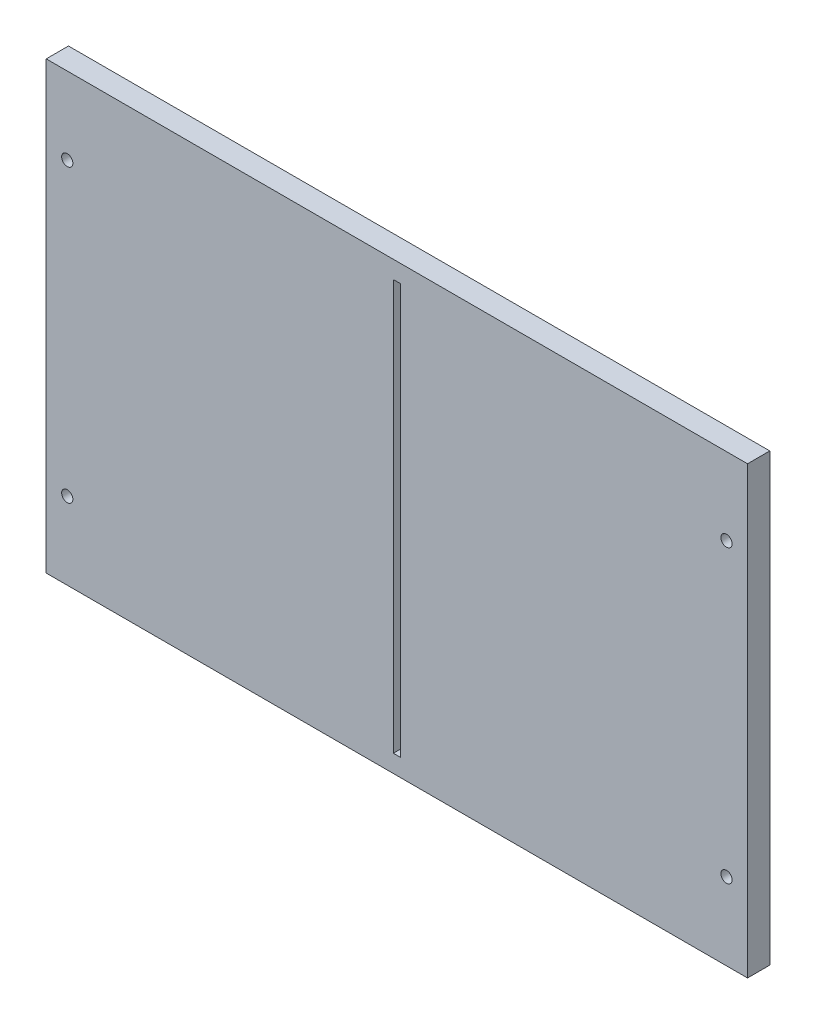
SolidWorks part; units mm, degrees
ref_plane "Front Plane" through (0, 0, 0) normal (0, 0, 1) x (1, 0, 0)
ref_plane "Top Plane" through (0, 0, 0) normal (0, 1, 0) x (1, 0, 0)
ref_plane "Right Plane" through (0, 0, 0) normal (1, 0, 0) x (0, 0, -1)
sketch "Sketch1" plane through (0, 0, 0) normal (0, 0, 1) x (1, 0, 0)
  line L0 (100, 127) -> (100, 0) construction
  line L1 (0, 0) -> (200, 0)
  line L2 (0, 0) -> (0, 127)
  line L3 (0, 127) -> (200, 127)
  line L4 (200, 0) -> (200, 127)
  line L5 (0, 63.5) -> (200, 63.5) construction
  circle A3 centre (6, 105) radius 1.6
  circle A7 centre (194, 105) radius 1.6
  circle A8 centre (194, 22) radius 1.6
  circle A9 centre (6, 22) radius 1.6
  dimension "D11" = 3.2
  dimension "D1" = 127
  dimension "D2" = 200
  dimension "D12" = 6
  dimension "D13" = 22
extrude "Wall" add sketch "Sketch1" along normal blind 6.35
sketch "Sketch2" [suppressed] plane through (0, 0, 6.35) normal (0, 0, 1) x (1, 0, 0)
  line L0 (135.35, 127) -> (135.35, 98.425) construction
  line L1 (270.7, 127) -> (0, 127) construction
  line L2 (135.35, 98.425) -> (66.6667, 98.425) construction
  line L3 (135.35, 98.425) -> (204.0333, 98.425) construction
  line L4 (0, 127) -> (0, 0) construction
  circle A0 centre (135.35, 98.425) radius 3.9687
  circle A1 centre (66.6667, 98.425) radius 3.9688
  circle A2 centre (204.0333, 98.425) radius 3.9687
  dimension "D2" = 7.9375
  dimension "D1" = 28.575
  dimension "D3" = 66.6667
extrude "RodSupportCutouts" [suppressed] cut sketch "Sketch2" against normal up to next
sketch "Sketch3" [suppressed] plane through (0, 0, 6.35) normal (0, 0, 1) x (1, 0, 0)
  line L1 (25.4, 88.9) -> (245.3, 88.9)
  line L2 (25.4, 88.9) -> (25.4, 114.3)
  line L3 (25.4, 114.3) -> (245.3, 114.3)
  line L4 (245.3, 88.9) -> (245.3, 114.3)
  line L5 (25.4, 88.9) -> (245.3, 114.3) construction
  line L6 (25.4, 114.3) -> (245.3, 88.9) construction
  line L7 (270.7, 127) -> (0, 127) construction
  line L8 (0, 127) -> (0, 0) construction
  point P0 (135.35, 101.6)
  point P9 (135.35, 127)
  dimension "D1" = 25.4
  dimension "D2" = 25.4
  dimension "D3" = 25.4
extrude "CannulaLargeCutout" [suppressed] cut sketch "Sketch3" against normal up to next
sketch "Sketch4" [suppressed] plane through (0, 0, 9.525) normal (0, 0, 1) x (1, 0, 0)
  line L0 (6, 103.5) -> (194, 103.5) construction
  line L1 (6, 105) -> (6, 22) construction
  line L2 (194, 105) -> (194, 22) construction
  line L3 (200, 127) -> (0, 127) construction
  line L4 (0, 127) -> (0, 0) construction
  circle A0 centre (60, 103.5) radius 6.35
  circle A1 centre (20, 103.5) radius 6.35
  circle A2 centre (100, 103.5) radius 6.35
  circle A3 centre (140, 103.5) radius 6.35
  circle A4 centre (60, 63.5) radius 6.35
  circle A5 centre (100, 63.5) radius 6.35
  circle A6 centre (140, 63.5) radius 6.35
  circle A7 centre (60, 23.5) radius 6.35
  circle A8 centre (100, 23.5) radius 6.35
  circle A9 centre (140, 23.5) radius 6.35
  circle A10 centre (20, 63.5) radius 6.35
  circle A11 centre (20, 23.5) radius 6.35
  circle A12 centre (180, 103.5) radius 6.35
  circle A13 centre (180, 63.5) radius 6.35
  circle A14 centre (180, 23.5) radius 6.35
  point P42 (100, 127)
  point P45 (0, 63.5)
  dimension "D3" = 12.7
  dimension "D1" = 5
  dimension "D2" = 3
extrude "CannulaHoles" [suppressed] cut sketch "Sketch4" against normal up to next
ref_plane "LeftBoundary" [suppressed] through (25.4, 0, 0) normal (-1, 0, 0) x (0, 0, 1)
ref_plane "RightBoundary" [suppressed] through (245.3, 0, 0) normal (1, 0, 0) x (0, 0, -1)
ref_plane "TopBoundary" [suppressed] through (0, 101.6, 0) normal (0, 1, 0) x (1, 0, 0)
ref_plane "BottomBoundary" [suppressed] through (0, 25.4, 0) normal (0, -1, 0) x (-1, 0, 0)
sketch "Sketch5" [suppressed] plane through (0, 0, 6.35) normal (0, 0, 1) x (1, 0, 0)
  line L4 (25.4, 3.4925) -> (25.4, -3.4925) construction
  line L5 (3.4925, 101.6) -> (-3.4925, 101.6) construction
  circle A0 centre (25.4, 101.6) radius 3.9687
  dimension "D1" = 7.9375
extrude "RodSupportCutout" [suppressed] cut sketch "Sketch5" along normal blind 3.35 from surface starting at face at (4.4, 22, 0)
pattern_linear "SupportPattern" [suppressed] count 7 spacing 36.65 count 5 spacing 19.05 of bodies 105
sketch "Sketch6" plane through (0, 0, 6.35) normal (0, 0, 1) x (1, 0, 0)
  line L1 (99, 122) -> (101, 122)
  line L2 (99, 122) -> (99, 5)
  line L3 (99, 5) -> (101, 5)
  line L4 (101, 122) -> (101, 5)
  line L9 (0, 0) -> (200, 0) construction
  line L10 (200, 0) -> (200, 127) construction
  point P7 (200, 57)
  dimension "D1" = 117
  dimension "D2" = 5
  dimension "D3" = 2
  dimension "D4" = 99
extrude "Cut-Extrude1" cut sketch "Sketch6" against normal through all
equation "\"Length\"= 283mm"
equation "\"Width\"= 225mm"
equation "\"WallThickness\"= 0.25in"
equation "\"UpperWaterJacketThickness\"= 28mm"
equation "\"SpacerHeight\"= 80.2mm"
equation "\"SpacerCornerWidth\"= 10mm"
equation "\"SpacerCornerHeight\"= 60.16mm"
equation "\"SpacerPegDiameter\"= 10mm"
equation "\"SpacerPegHeight\"= 10mm"
equation "\"TubingShort\"= 110mm"
equation "\"TubingLong\"= 175mm"
equation "\"PlateLength\"= 252mm"
equation "\"PlateWidth\"= 190mm"
equation "\"PlateHoleDiameter\"= 5.9mm"
equation "\"PlateHoleBottom\"= 2mm"
equation "\"PlateHoleSide\"= 1.55mm"
equation "\"PlateHoleSpacing\"= 3.1mm"
equation "\"PlateThickness\"= 1.55mm"
equation "\"ReservoirBottom\"= 12.5mm"
equation "\"ReservoirSupportWidth\"= 12mm"
equation "\"ReservoirSupportHeight\"= 15.1mm"
equation "\"ReservoirSupportPlacementHeight\"= 50mm"
equation "\"ReservoirHoleDiameter\"= 12.7mm"
equation "\"ReservoirHoleRight\"= 25mm"
equation "\"ReservoirHoleTop\"= \"ReservoirSupportPlacementHeight\""
equation "\"ReservoirHeight\"= 90mm"
equation "\"ReservoirPortBottom\"= 4mm"
equation "\"ReservoirPortTop\"= 10mm"
equation "\"ReservoirPortWidth\"= 101mm"
equation "\"CustomSpacerHeight\"= 5in"
equation "\"CustomSpacerRodHoleHeight\"= .75in"
equation "\"CustomSpacerRodHoleDiameter\"= .3125in"
equation "\"ScrewBlockSide\"= 12mm"
equation "\"ScrewBlockUpperHeight\"= 16mm"
equation "\"ScrewBlockLowerHeight\"= 16mm"
equation "\"InternalLength\"= 258mm"
equation "\"InternalWidth\"= 200mm"
equation "\"CustomSpacerPegHeight\"= 1in"
equation "\"CustomSpacerScrewBore\"=3.2mm"
equation "\"CustomSpacerScrewDepth\"=10mm"
equation "\"D1@Sketch1\"=\"CustomSpacerHeight\""
equation "\"D2@Sketch1\"=\"WallLength\""
equation "\"D11@Sketch1\"=\"CustomSpacerScrewBore\""
equation "\"D12@Sketch1\"   = \"ScrewBlockSide\"/2"
equation "\"D13@Sketch1\"=\"ScrewBlockUpperHeight\"+\"ScrewBlockSide\"/2"
equation "\"D1@Wall\" = \"WallThickness\""
equation "\"D1@Sketch2\"=\"CustomSpacerRodHoleHeight\" + \"CustomSpacerRodHoleDiameter\" +0.0625in"
equation "\"D2@Sketch2\"=\"CustomSpacerRodHoleDiameter\""
equation "\"D3@Sketch2\"=\"InternalWidth\" / 3"
equation "\"D1@Sketch3\"=1in"
equation "\"WallLength\"= \"InternalWidth\""
equation "\"D1@Sketch5\"=\"CustomSpacerRodHoleDiameter\""
equation "\"D1@RodSupportCutout\"      = \"WallThickness\" - 3"
